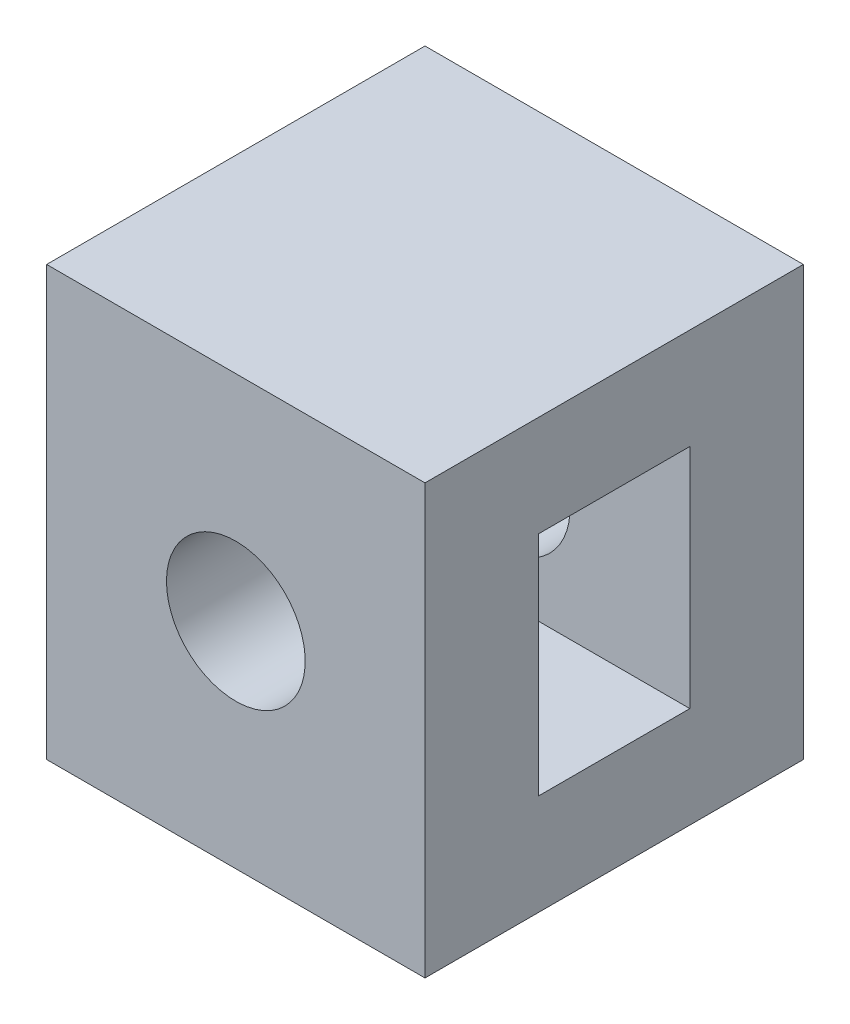
SolidWorks part; units mm, degrees
material "Malleable Cast Iron"
ref_plane "Front Plane" through (0, 0, 0) normal (0, 0, 1) x (1, 0, 0)
ref_plane "Top Plane" through (0, 0, 0) normal (0, 1, 0) x (1, 0, 0)
ref_plane "Right Plane" through (0, 0, 0) normal (1, 0, 0) x (0, 0, -1)
sketch "Sketch1" plane through (0, 0, 0) normal (0, 1, 0) x (1, 0, 0)
  line L0 (0, 0) -> (15, 0)
  line L1 (15, 0) -> (15, -15)
  line L2 (15, -15) -> (0, -15)
  line L3 (0, -15) -> (0, 0)
  dimension "D1" = 15
  dimension "D2" = 15
extrude "Boss-Extrude1" add sketch "Sketch1" along normal blind 17
sketch "Sketch2" plane through (15, 0, 0) normal (1, 0, 0) x (0, 0, -1)
  line L9 (-15, 17) -> (0, 17) construction
  line L10 (-10.5, 17) -> (-4.5, 17)
  line L11 (-10.5, 4) -> (-4.5, 4)
  line L12 (-4.5, 4) -> (-4.5, 13)
  line L13 (-4.5, 13) -> (-10.5, 13)
  line L14 (-10.5, 13) -> (-10.5, 4)
extrude "Cut-Extrude1" cut sketch "Sketch2" against normal blind 12 contours L11 L12 L13 L14
sketch "Sketch4" plane through (15, 0, 0) normal (1, 0, 0) x (0, 0, -1)
  line L0 (-4.5, 8.5) -> (0, 8.5) construction
  line L3 (-4.5, 4) -> (-4.5, 13) construction
  line L4 (0, 17) -> (0, 0) construction
sketch "Sketch5" plane through (0, 0, 0) normal (0, 0, -1) x (-1, 0, 0)
  line L0 (-15, 8.5) -> (-7.5, 8.5) construction
  line L1 (-15, 17) -> (-15, 0) construction
  circle A1 centre (-7.5, 8.5) radius 2.75
  dimension "D1" = 5.5
  dimension "D2" = 7.5
extrude "Cut-Extrude2" cut sketch "Sketch5" against normal through all contours A1
